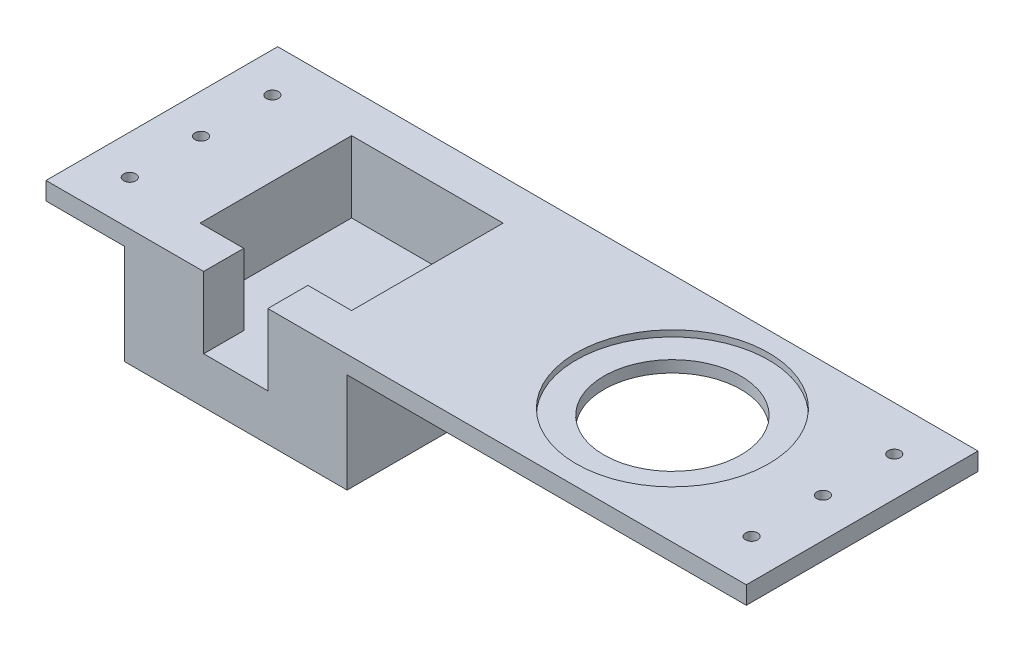
SolidWorks part; units mm, degrees
ref_plane "Front Plane" through (0, 0, 0) normal (0, 0, 1) x (1, 0, 0)
ref_plane "Top Plane" through (0, 0, 0) normal (0, 1, 0) x (1, 0, 0)
ref_plane "Right Plane" through (0, 0, 0) normal (1, 0, 0) x (0, 0, -1)
sketch "Sketch2" plane through (0, 0, 0) normal (0, 1, 0) x (1, 0, 0)
  line L1 (98.225, 32.5) -> (-98.225, 32.5)
  line L2 (98.225, 32.5) -> (98.225, -32.5)
  line L3 (98.225, -32.5) -> (-98.225, -32.5)
  line L4 (-98.225, 32.5) -> (-98.225, -32.5)
  line L5 (98.225, 32.5) -> (-98.225, -32.5) construction
  line L6 (98.225, -32.5) -> (-98.225, 32.5) construction
  point P0 (0, 0)
  dimension "D1" = 65
  dimension "D2" = 196.45
extrude "Boss-Extrude1" add sketch "Sketch2" along normal blind 5 contours L4 L3 L2 L1
sketch "Sketch3" plane through (0, 0, 0) normal (0, 1, 0) x (1, 0, 0)
  line L0 (-45, 0) -> (0, 0) construction
  line L1 (0, 0) -> (45, 0) construction
  line L6 (-66.25, -21.25) -> (-54, -21.25)
  line L7 (-66.25, -21.25) -> (-66.25, 21.25)
  line L8 (-23.75, -21.25) -> (-23.75, 21.25)
  line L9 (-66.25, 21.25) -> (-23.75, 21.25)
  line L10 (-66.25, -21.25) -> (-23.75, 21.25) construction
  line L11 (-23.75, -21.25) -> (-66.25, 21.25) construction
  line L12 (-54, -21.25) -> (-54, -32.5)
  line L13 (98.225, -32.5) -> (-98.225, -32.5) construction
  line L14 (-54, -32.5) -> (-36, -32.5) construction
  line L15 (-36, -32.5) -> (-36, -21.25)
  line L16 (-36, -21.25) -> (-23.75, -21.25)
  line L17 (98.225, 32.5) -> (-98.225, 32.5) construction
  line L19 (-13.75, -32.5) -> (-13.75, 32.5)
  line L20 (-13.75, 32.5) -> (-76.25, 32.5)
  line L21 (-76.25, -32.5) -> (-76.25, 32.5)
  line L22 (-13.75, -32.5) -> (-76.25, 32.5) construction
  line L23 (-13.75, 32.5) -> (-76.25, -32.5) construction
  line L24 (-36, -21.25) -> (-54, -21.25) construction
  line L25 (-76.25, -32.5) -> (-54, -32.5)
  line L26 (-36, -32.5) -> (-13.75, -32.5)
  circle A1 centre (45, 0) radius 19.2
  point P7 (-45, 0)
  point P23 (-45, -21.25)
  dimension "D1" = 38.4
  dimension "D2" = 18
  dimension "D4" = 90
  dimension "D3" = 42.5
  dimension "D5" = 10
extrude "Boss-Extrude2" add sketch "Sketch3" against normal blind 28 contours L15 L26 L19 L20 L21 L25 L12 L6 L7 L9 L8 L16 region at (-60.125, 0, 22.1517)
sketch "Sketch12" plane through (0, -28, 0) normal (0, -1, 0) x (1, 0, 0)
  line L8 (-36, 21.25) -> (-36, 32.5)
  line L9 (-36, 32.5) -> (-54, 32.5)
  line L10 (-54, 32.5) -> (-54, 21.25)
  line L11 (-54, 21.25) -> (-66.25, 21.25)
  line L12 (-66.25, 21.25) -> (-66.25, -21.25)
  line L13 (-66.25, -21.25) -> (-23.75, -21.25)
  line L14 (-23.75, -21.25) -> (-23.75, 21.25)
  line L15 (-23.75, 21.25) -> (-36, 21.25)
  line L16 (-36, 21.25) -> (-36, 32.5)
  line L17 (-36, 32.5) -> (-54, 32.5)
  line L18 (-54, 32.5) -> (-54, 21.25)
  line L19 (-54, 21.25) -> (-66.25, 21.25)
  line L20 (-66.25, 21.25) -> (-66.25, -21.25)
  line L21 (-66.25, -21.25) -> (-23.75, -21.25)
  line L22 (-23.75, -21.25) -> (-23.75, 21.25)
  line L23 (-23.75, 21.25) -> (-36, 21.25)
  dimension "D1" = 0
extrude "Boss-Extrude3" add sketch "Sketch12" against normal blind 20
extrude "Cut-Extrude9" cut sketch "Sketch12<2>" along normal blind 20 from surface starting at face at (0, 5, 0)
sketch "Sketch12<2>" plane through (0, -28, 0) normal (0, -1, 0) x (1, 0, 0) same geometry as "Sketch12"
sketch "Sketch4" plane through (0, 5, 0) normal (0, 1, 0) x (1, 0, 0)
  circle A0 centre (45, 0) radius 26.99
  dimension "D1" = 53.98
extrude "Cut-Extrude3" cut sketch "Sketch4" against normal blind 1.74
extrude "Cut-Extrude10" cut sketch "Sketch3<4>" along normal blind 20 contours A1 region at (45, 0, 0)
sketch "Sketch3<4>" plane through (0, 0, 0) normal (0, 1, 0) x (1, 0, 0) same geometry as "Sketch3"
sketch "Sketch13" plane through (0, 5, 0) normal (0, 1, 0) x (1, 0, 0)
  line L0 (-87.225, 32.5) -> (-87.225, -32.5) construction
  line L1 (98.225, 32.5) -> (-98.225, 32.5) construction
  line L2 (-54, -32.5) -> (-98.225, -32.5) construction
  line L3 (87.225, 32.5) -> (87.225, -32.5) construction
  line L4 (98.225, -32.5) -> (-36, -32.5) construction
  line L5 (-98.225, 32.5) -> (-98.225, -32.5) construction
  line L6 (98.225, 32.5) -> (98.225, -32.5) construction
  point P14 (87.225, 0)
  point P15 (-87.225, 0)
  point P16 (-87.225, 20)
  point P17 (-87.225, -20)
  point P18 (87.225, 20)
  point P19 (87.225, -20)
  dimension "D1" = 11
  dimension "D2" = 11
  dimension "D3" = 20
  dimension "D4" = 20
hole_wizard "M3 Clearance Hole1" positions "Sketch16" profile "Sketch15" hole size "M3" standard "ANSI Metric" end condition through all
sketch "Sketch16" plane through (0, 5, 0) normal (0, 1, 0) x (1, 0, 0)
  point P0 (-87.225, 20)
  point P3 (-87.225, 0)
  point P6 (-87.225, -20)
  point P9 (87.225, -20)
  point P12 (87.225, 0)
  point P15 (87.225, 20)
sketch "Sketch15" plane through (-87.225, 5, -20) normal (1, 0, 0) x (0, 0, 1)
  line L0 (0, 0) -> (0, 33)
  line L1 (0, 33) -> (1.7, 33)
  line L2 (1.7, 33) -> (1.7, 0)
  line L5 (1.7, 0) -> (0, 0)
  line L11 (0, -6.35) -> (0, 107.95) construction
  dimension "Thru Hole Dia." = 3.4
  dimension "Thru Hole Depth" = 33
